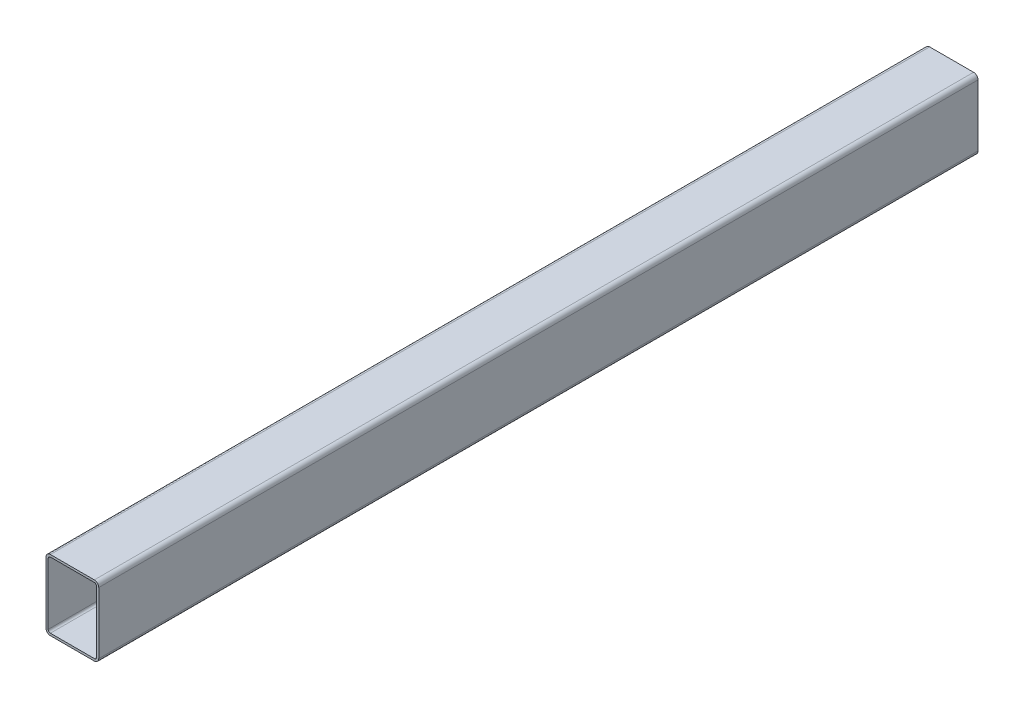
SolidWorks part; units mm, degrees
material "Plain Carbon Steel"
ref_plane "Front Plane" through (0, 0, 0) normal (0, 0, 1) x (1, 0, 0)
ref_plane "Top Plane" through (0, 0, 0) normal (0, 1, 0) x (1, 0, 0)
ref_plane "Right Plane" through (0, 0, 0) normal (1, 0, 0) x (0, 0, -1)
sketch "Sketch4" plane through (0, 0, 0) normal (0, 0, 1) x (1, 0, 0)
  line L4 (31.75, -47.6907) -> (-31.75, -47.6907)
  line L5 (34.925, 44.3843) -> (34.925, -44.5157)
  line L6 (-34.925, -44.5157) -> (-34.925, 44.3843)
  line L7 (-31.75, 47.5593) -> (31.75, 47.5593)
  line L8 (31.75, -50.8657) -> (-31.75, -50.8657)
  line L9 (38.1, 44.3843) -> (38.1, -44.5157)
  line L10 (-31.75, 50.7343) -> (31.75, 50.7343)
  line L11 (-38.1, -44.5157) -> (-38.1, 44.3843)
  arc A4 (-34.925, -44.5157) -> (-31.75, -47.6907) centre (-31.75, -44.5157) ccw
  arc A5 (31.75, -47.6907) -> (34.925, -44.5157) centre (31.75, -44.5157) ccw
  arc A6 (34.925, 44.3843) -> (31.75, 47.5593) centre (31.75, 44.3843) ccw
  arc A7 (-31.75, 47.5593) -> (-34.925, 44.3843) centre (-31.75, 44.3843) ccw
  arc A8 (-38.1, -44.5157) -> (-31.75, -50.8657) centre (-31.75, -44.5157) ccw
  arc A9 (31.75, -50.8657) -> (38.1, -44.5157) centre (31.75, -44.5157) ccw
  arc A10 (38.1, 44.3843) -> (31.75, 50.7343) centre (31.75, 44.3843) ccw
  arc A11 (-31.75, 50.7343) -> (-38.1, 44.3843) centre (-31.75, 44.3843) ccw
  dimension "D1" = 3.175
extrude "Boss-Extrude1" add sketch "Sketch4" along normal mid plane 1270 separate body
equation "\"M5_tap\"=4.2mm       ' Below you can do mesurements as follows: cm, mm, ft, in, m, "
equation "\"M5_clearence\"=5.5mm"
equation "\"M6_tap\"=5mm"
equation "\"M6_clearence\"=6.6mm"
